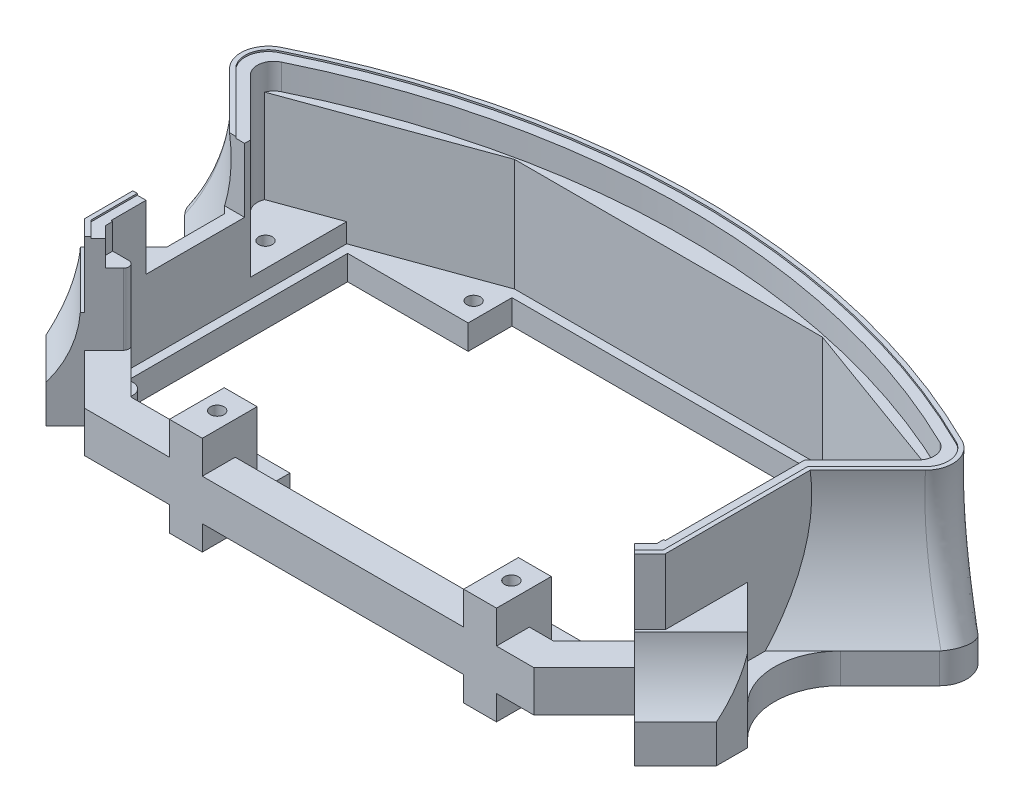
SolidWorks part; units mm, degrees
material "ABS"
ref_plane "Front Plane" through (0, 0, 0) normal (0, 0, 1) x (1, 0, 0)
ref_plane "Top Plane" through (0, 0, 0) normal (0, 1, 0) x (1, 0, 0)
ref_plane "Right Plane" through (0, 0, 0) normal (1, 0, 0) x (0, 0, -1)
sketch "Sketch1" plane through (0, 0, 0) normal (0, 1, 0) x (1, 0, 0)
  line L0 (53, 80) -> (53, 129.1478)
  line L1 (-53, 129.1478) -> (-53, 80)
  line L2 (-41, 68) -> (41, 68)
  line L3 (-53, 80) -> (-41, 68)
  line L4 (41, 68) -> (53, 80)
  circle A0 centre (0, 0) radius 140 construction
  arc A1 (53, 129.1478) -> (-53, 129.1478) centre (0, 0) ccw
  dimension "D1" = 280
  dimension "D3" = 139.6
  dimension "D2" = 106
  dimension "D4" = 68
  dimension "D5" = 80
  dimension "D6" = 135
  dimension "D7" = 135
extrude "Boss-Extrude1" add sketch "Sketch1" along normal blind 30
sketch "Sketch2" plane through (0, 30, 0) normal (0, 1, 0) x (1, 0, 0)
  line L0 (-49, 84) -> (49, 84)
  line L1 (49, 84) -> (49, 124)
  line L2 (49, 124) -> (27, 124)
  line L3 (27, 124) -> (27, 132)
  line L4 (27, 132) -> (-27, 132)
  line L5 (-27, 132) -> (-27, 124)
  line L6 (-27, 124) -> (-49, 124)
  line L7 (-49, 124) -> (-49, 84)
  line L12 (-53, 129.1478) -> (-53, 80) construction
  dimension "D1" = 48
  dimension "D2" = 98
  dimension "D3" = 8
  dimension "D4" = 84
  dimension "D5" = 22
  dimension "D6" = 4
extrude "Cut-Extrude1" cut sketch "Sketch2" against normal up to next
sketch "Sketch3" plane through (0, 30, 0) normal (0, 1, 0) x (1, 0, 0)
  line L0 (-50, 83) -> (50, 83) construction
  line L1 (50, 83) -> (50, 125) construction
  line L2 (50, 125) -> (28, 133) construction
  line L3 (28, 133) -> (-28, 133) construction
  line L4 (-28, 133) -> (-50, 125) construction
  line L5 (-50, 125) -> (-50, 83) construction
  line L7 (-49, 84) -> (-49, 124) construction
  line L8 (-50.6, 125.4203) -> (-50.6, 82.4)
  line L9 (-50.6, 82.4) -> (50.6, 82.4)
  line L10 (50.6, 82.4) -> (50.6, 125.4203)
  line L11 (50.6, 125.4203) -> (28.1057, 133.6)
  line L12 (28.1057, 133.6) -> (-28.1057, 133.6)
  line L13 (-28.1057, 133.6) -> (-50.6, 125.4203)
  line L16 (-49, 84) -> (49, 84) construction
  dimension "D1" = 50
  dimension "D2" = 22
  dimension "D3" = 8
  dimension "D4" = 1
  dimension "D5" = 1
  dimension "D6" = 100
  dimension "D7" = 0.6
extrude "Cut-Extrude2" cut sketch "Sketch3" against normal offset from surface (25.5 mm away) 4.5 up to face at (0, 0, -116)
sketch "Sketch5" plane through (0, 30, 0) normal (0, 1, 0) x (1, 0, 0)
  line L1 (-37.48, 68.91) -> (43.8, 68.91) construction
  line L2 (-37.48, 68.91) -> (-37.48, 122.25) construction
  line L3 (-37.48, 122.25) -> (43.8, 122.25) construction
  line L4 (43.8, 68.91) -> (43.8, 122.25) construction
  line L6 (-37.88, 68.51) -> (-37.88, 122.65)
  line L7 (-37.88, 122.65) -> (44.2, 122.65)
  line L8 (44.2, 68.51) -> (44.2, 122.65)
  line L9 (-37.88, 68.51) -> (44.2, 68.51)
  dimension "D1" = 68.91
  dimension "D2" = 43.8
  dimension "D3" = 81.28
  dimension "D4" = 53.34
  dimension "D5" = 0.4
extrude "Cut-Extrude4" cut sketch "Sketch5" against normal offset from surface (12 mm away) 18 up to face at (0, 0, -116)
sketch "Sketch4" plane through (0, 18, 0) normal (0, 1, 0) x (1, 0, 0)
  circle A0 centre (31.18, 73.72) radius 1.25
  circle A1 centre (-22.53, 73.72) radius 1.25
  dimension "D2" = 2.5
  dimension "D1" = 22.53
  dimension "D3" = 6.28
  dimension "D4" = 53.71
extrude "Cut-Extrude3" cut sketch "Sketch4" against normal up to next
sketch "Sketch6" plane through (0, 30, 0) normal (0, 1, 0) x (1, 0, 0)
  line L5 (53, 80) -> (53, 129.1478) construction
  line L6 (-53, 129.1478) -> (-53, 80) construction
  line L7 (-41, 68) -> (41, 68) construction
  line L8 (-53, 80) -> (-41, 68) construction
  line L9 (44.2, 71.2) -> (53, 80) construction
  line L25 (50.3, 81.1184) -> (50.3, 127.3245)
  line L26 (39.8816, 70.7) -> (50.3, 81.1184)
  line L27 (-39.8816, 70.7) -> (39.8816, 70.7)
  line L28 (-50.3, 81.1184) -> (-39.8816, 70.7)
  line L29 (-50.3, 127.3245) -> (-50.3, 81.1184)
  arc A1 (53, 129.1478) -> (-53, 129.1478) centre (0, 0) ccw construction
  arc A8 (50.3, 127.3245) -> (-50.3, 127.3245) centre (0, 0) ccw
  dimension "D3" = 2.7
  dimension "D1" = 2.7
  dimension "D2" = 2.7
  dimension "D4" = 2.7
  dimension "D5" = 2.7
  dimension "D6" = 2.7
extrude "Cut-Extrude5" cut sketch "Sketch6" against normal blind 5
sketch "Sketch7" plane through (0, 0, 0) normal (0, -1, 0) x (1, 0, 0)
  line L0 (73.4563, -118.7111) -> (53, -98.2548)
  line L1 (53, -80) -> (53, -129.1478) construction
  line L2 (53, -98.2548) -> (53, -129.1478)
  line L3 (0, 0) -> (103.3995, -103.3995) construction
  arc A0 (53, -129.1478) -> (73.4563, -118.7111) centre (0, 0) ccw
  arc A1 (-53, -129.1478) -> (53, -129.1478) centre (0, 0) ccw construction
  dimension "D1" = 45
  dimension "D2" = 32
extrude "Boss-Extrude2" add sketch "Sketch7" against normal up to surface (30 mm away) up to face at (0.5945, 30, -93.6394)
ref_plane "Plane1" through (96.0837, 0, -96.0837) normal (-0.7071, 0, 0.7071) x (0, -1, 0)
sketch "Sketch8" plane through (96.0837, 0, -96.0837) normal (-0.7071, 0, 0.7071) x (0, -1, 0)
  line L0 (-30, -32) -> (0, -32) construction
  circle A0 centre (-26, 0) radius 38
  dimension "D3" = 76
  dimension "D1" = 32
  dimension "D2" = 26
extrude "Cut-Extrude6" cut sketch "Sketch8" along normal up to surface (98.9296 mm away) up to face at (53, 18.75, -84.5637)
mirror "Mirror1" about plane through (0, 0, 0) normal (1, 0, 0) of "Boss-Extrude2"
ref_plane "Plane2" through (-96.0837, 0, -96.0837) normal (0.7071, 0, 0.7071) x (0, -1, 0)
sketch "Sketch9" plane through (-96.0837, 0, -96.0837) normal (0.7071, 0, 0.7071) x (0, -1, 0)
  line L0 (-30, 32) -> (0, 32) construction
  circle A0 centre (-26, 0) radius 38
  dimension "D1" = 76
  dimension "D2" = 32
  dimension "D3" = 26
extrude "Cut-Extrude7" cut sketch "Sketch9" along normal up to surface (22.9296 mm away) up to face at (-53, 18.75, -93.6911)
fillet "Fillet2" radius 5 4 edges at (69.0949, 16.9868, -121.3015) (73.4563, 2.753, -118.7111) (-73.4563, 2.753, -118.7111) (-68.9598, 17.6248, -121.3784)
sketch "Sketch11" plane through (0, 4.5, 0) normal (0, 1, 0) x (1, 0, 0)
  line L0 (-49, 124) -> (-27, 124) construction
  circle A0 centre (-30, 128) radius 1.25
  circle A1 centre (30, 128) radius 1.25
  dimension "D2" = 2.5
  dimension "D1" = 4
  dimension "D3" = 60
  dimension "D4" = 30
extrude "Cut-Extrude9" cut sketch "Sketch11" against normal up to next
sketch "Sketch12" plane through (0, 30, 0) normal (0, 1, 0) x (1, 0, 0)
  line L0 (-60.9187, 118.1786) -> (-50.3, 107.5599)
  line L2 (-50.3, 107.5599) -> (-50.3, 127.3245)
  line L3 (-63.5251, 116.9667) -> (-53, 106.4416) construction
  arc A0 (-50.3, 127.3245) -> (-60.1147, 122.9952) centre (0, 0) ccw
  arc A1 (-60.1147, 122.9952) -> (-60.9187, 118.1786) centre (-58.7974, 120.3) ccw
  arc A3 (62.1871, 124.9837) -> (-62.1871, 124.9837) centre (0, 0) ccw construction
  dimension "D1" = 2.7
  dimension "D2" = 3
extrude "Cut-Extrude10" cut sketch "Sketch12" against normal offset from surface (22 mm away) 8 up to face at (30, 0, -126.75)
sketch "Sketch14" plane through (0, 8, 0) normal (0, 1, 0) x (1, 0, 0)
  line L0 (-50.3, 127.3245) -> (-61.577, 123.2238)
  line L1 (-61.577, 123.2238) -> (-61.577, 121.4286)
  line L2 (-61.577, 121.4286) -> (-50.3, 125.5293)
  line L3 (-50.3, 125.5293) -> (-50.3, 127.3245)
  line L4 (-50.6, 125.4203) -> (-28.1057, 133.6) construction
  arc A0 (-60.1147, 122.9952) -> (-60.9187, 118.1786) centre (-58.7974, 120.3) ccw construction
extrude "Boss-Extrude3" add sketch "Sketch14" along normal up to surface (17 mm away) up to face at (0, 25, -130.4139)
mirror "Mirror2" about plane through (0, 0, 0) normal (1, 0, 0) of "Boss-Extrude3", "Cut-Extrude10"
sketch "Sketch15" plane through (0, 30, 0) normal (0, 1, 0) x (1, 0, 0)
  line L0 (-50.1716, 77.1716) -> (-43.3431, 84)
  line L1 (-53, 80) -> (-41, 68) construction
  line L2 (49, 84) -> (-49, 84) construction
  line L3 (-43.3431, 84) -> (43.3431, 84)
  line L4 (43.3431, 84) -> (50.1716, 77.1716)
  line L5 (41, 68) -> (41.51, 68.51) construction
  line L6 (50.1716, 77.1716) -> (41, 68)
  line L7 (41, 68) -> (-41, 68)
  line L8 (-41, 68) -> (-50.1716, 77.1716)
  dimension "D1" = 4
  dimension "D2" = 4
extrude "Cut-Extrude12" cut sketch "Sketch15" against normal up to surface (12 mm away) up to face at (-22.53, 18, -72.47)
sketch "Sketch16" plane through (0, 18, 0) normal (0, 1, 0) x (1, 0, 0)
  line L0 (-50.1716, 77.1716) -> (-44.9431, 82.4)
  line L1 (-44.9431, 82.4) -> (-25.53, 82.4)
  line L2 (50.6, 82.4) -> (-50.6, 82.4) construction
  line L3 (-25.53, 82.4) -> (-25.53, 68)
  line L4 (41, 68) -> (-41, 68) construction
  line L5 (-25.53, 68) -> (-41, 68)
  line L6 (-41, 68) -> (-50.1716, 77.1716) construction
  line L7 (-41, 68) -> (-50.1716, 77.1716)
  line L8 (44.9431, 82.4) -> (-44.9431, 82.4) construction
  line L9 (-19.53, 68) -> (28.18, 68)
  line L10 (-19.53, 68) -> (-19.53, 82.4)
  line L11 (-19.53, 82.4) -> (28.18, 82.4)
  line L12 (28.18, 68) -> (28.18, 82.4)
  line L13 (34.18, 82.4) -> (34.18, 68)
  line L14 (34.18, 68) -> (41, 68)
  line L15 (41, 68) -> (50.1716, 77.1716)
  line L16 (50.1716, 77.1716) -> (44.9431, 82.4)
  line L17 (44.9431, 82.4) -> (34.18, 82.4)
  circle A0 centre (31.18, 73.72) radius 1.25 construction
  circle A3 centre (-22.53, 73.72) radius 1.25 construction
  dimension "D1" = 3
  dimension "D2" = 3
  dimension "D3" = 3
  dimension "D4" = 3
extrude "Cut-Extrude13" cut sketch "Sketch16" against normal blind 6
sketch "Sketch20" plane through (0, 0, 0) normal (0, -1, 0) x (1, 0, 0)
  line L0 (-50.1716, -77.1716) -> (-41, -68)
  line L1 (-41, -68) -> (-25.53, -68)
  line L2 (-25.53, -68) -> (-25.53, -84)
  line L3 (-25.53, -84) -> (-43.3431, -84)
  line L4 (-43.3431, -84) -> (-50.1716, -77.1716)
  line L5 (-19.53, -84) -> (28.18, -84)
  line L6 (-19.53, -84) -> (-19.53, -68)
  line L7 (-19.53, -68) -> (28.18, -68)
  line L8 (28.18, -84) -> (28.18, -68)
  line L9 (34.18, -68) -> (34.18, -84)
  line L10 (34.18, -84) -> (43.3431, -84)
  line L11 (43.3431, -84) -> (50.1716, -77.1716)
  line L12 (50.1716, -77.1716) -> (41, -68)
  line L13 (41, -68) -> (34.18, -68)
  line L14 (-41, -68) -> (41, -68) construction
  line L15 (41, -68) -> (53, -80) construction
  line L16 (49, -84) -> (-49, -84) construction
  line L17 (-53, -80) -> (-41, -68) construction
extrude "Cut-Extrude17" cut sketch "Sketch20" against normal up to surface (4.5 mm away) up to face at (30, 4.5, -126.75)
fillet "Fillet4" radius 2 2 edges at (43.3431, 2.25, -84) (-43.3431, 2.25, -84)
sketch "Sketch17" plane through (0, 0, 0) normal (0, -1, 0) x (1, 0, 0)
  circle A0 centre (-55, -115) radius 1.25
  circle A1 centre (55, -115) radius 1.25
  dimension "D1" = 2.5
  dimension "D2" = 115
  dimension "D3" = 55
  dimension "D4" = 55
extrude "Cut-Extrude14" cut sketch "Sketch17" against normal blind 12
fillet "Fillet3" radius 1 2 edges at (44.9431, 18.5, -82.4) (-44.9431, 18.5, -82.4)
sketch "Sketch18" plane through (0, 18, 0) normal (0, 1, 0) x (1, 0, 0)
  line L0 (34.18, 82.4) -> (34.18, 68) construction
  line L1 (-25.53, 82.4) -> (34.18, 82.4)
  line L2 (-25.53, 82.4) -> (-25.53, 78)
  line L3 (-25.53, 78) -> (34.18, 78)
  line L4 (34.18, 82.4) -> (34.18, 78)
  line L5 (-19.53, 68) -> (-25.53, 68) construction
  dimension "D1" = 10
extrude "Cut-Extrude15" cut sketch "Sketch18" against normal up to surface (6 mm away) up to face at (-39.2781, 12, -76.4835)
sketch "Sketch19" plane through (0, 30, 0) normal (0, 1, 0) x (1, 0, 0)
  line L1 (-58, 106.7916) -> (-49, 106.7916)
  line L2 (-58, 106.7916) -> (-58, 88.7916)
  line L3 (-58, 88.7916) -> (-49, 88.7916)
  line L4 (-49, 106.7916) -> (-49, 88.7916)
  line L5 (-53, 106.4416) -> (-53, 80) construction
  line L6 (-49, 84) -> (-49, 124) construction
  circle A0 centre (-22.53, 73.72) radius 1.25 construction
  dimension "D1" = 15.0716
  dimension "D2" = 18
  dimension "D3" = 5
extrude "Cut-Extrude16" cut sketch "Sketch19" against normal up to surface (12 mm away) up to face at (-22.53, 18, -73)
sketch "Sketch21" plane through (0, 30, 0) normal (0, 1, 0) x (1, 0, 0)
  line L10 (-53, 105.5357) -> (-53, 88.7916) construction
  line L13 (52.2, 80) -> (52.2, 106.7729)
  line L14 (52.2, 106.7729) -> (62.9594, 117.5324)
  line L15 (-62.9594, 117.5324) -> (-52.7843, 107.3573)
  line L16 (52.2, 80.3314) -> (52.2, 106.7729)
  line L17 (52.2, 106.7729) -> (62.9594, 117.5324)
  line L18 (-62.9594, 117.5324) -> (-52.2, 106.7729)
  line L19 (-52.2, 106.7729) -> (-52.2, 80.3314)
  line L20 (-52.2, 80.3314) -> (-49.6059, 77.7373)
  line L21 (-46.6503, 80.6929) -> (-50.1716, 77.1716) construction
  line L22 (-49.6059, 77.7373) -> (49.6059, 77.7373)
  line L27 (50.1716, 77.1716) -> (46.6503, 80.6929) construction
  line L31 (49.6059, 77.7373) -> (52.2, 80.3314)
  line L33 (50.1716, 77.1716) -> (48.2624, 79.0808) construction
  line L34 (50.1716, 77.1716) -> (53, 80) construction
  line L35 (-53, 80) -> (-50.1716, 77.1716) construction
  arc A6 (61.8307, 124.2675) -> (-61.8307, 124.2675) centre (0, 0) ccw
  arc A7 (61.8307, 124.2675) -> (-61.8307, 124.2675) centre (0, 0) ccw
  spline S11 degree 3 poles (-2791.6803, -793.6282) (-151.1922, 208.4655) (47.8929, 98.3145) (63.3918, 118.0343) (63.4863, 118.1707) (63.7432, 118.5921) (63.884, 118.9004) (64.0846, 119.5295) (64.1477, 119.857) (64.1947, 120.5225) (64.1784, 120.8524) (64.0962, 121.3423) (64.0584, 121.5068) (63.9649, 121.8259) (63.9091, 121.9814) (63.7145, 122.4378) (63.5472, 122.7299) (63.1503, 123.2644) (62.9241, 123.5045) (41.0501, 141.8435) (-151.6347, -61.6595) (1792.5456, -2310.831) knots -9.381466 -9.381466 -9.381466 -9.381466 0.0625 0.0625 0.125 0.125 0.25 0.25 0.375 0.375 0.5 0.5 0.5625 0.5625 0.625 0.625 0.75 0.75 0.875 0.875 11.418904 11.418904 11.418904 11.418904 only from (62.9594, 117.5324) to (61.8307, 124.2675)
  spline S12 degree 3 poles (2933.466, 32.8068) (113.3304, -31.1396) (-41.1568, 137.8252) (-62.4023, 123.9288) (-62.5359, 123.8296) (-62.9156, 123.5123) (-63.1493, 123.2653) (-63.5445, 122.7339) (-63.711, 122.4452) (-63.974, 121.8299) (-64.0669, 121.5128) (-64.15, 121.0237) (-64.1683, 120.8561) (-64.1847, 120.5237) (-64.1829, 120.3586) (-64.16, 120.0292) (-64.1388, 119.8649) (-64.0769, 119.5398) (-64.0357, 119.3767) (-63.8846, 118.9013) (-63.7481, 118.6013) (-63.4897, 118.1756) (-63.394, 118.0374) (-47.2585, 97.4867) (150.4821, 235.4732) (2678.3171, -1087.2581) knots -9.468277 -9.468277 -9.468277 -9.468277 0.0625 0.0625 0.125 0.125 0.25 0.25 0.375 0.375 0.5 0.5 0.5625 0.5625 0.625 0.625 0.6875 0.6875 0.75 0.75 0.875 0.875 0.9375 0.9375 10.676928 10.676928 10.676928 10.676928 only from (-61.8307, 124.2675) to (-62.9594, 117.5324)
  spline S13 degree 3 poles (62.9594, 117.5324) (63.0781, 117.651) (63.188, 117.775) (63.3918, 118.0343) (63.4863, 118.1707) (63.7432, 118.5921) (63.884, 118.9004) (64.0846, 119.5295) (64.1477, 119.857) (64.1947, 120.5225) (64.1784, 120.8524) (64.0962, 121.3423) (64.0584, 121.5068) (63.9649, 121.8259) (63.9091, 121.9814) (63.7145, 122.4378) (63.5472, 122.7299) (63.1503, 123.2644) (62.9241, 123.5045) (62.4115, 123.9342) (62.1312, 124.118) (61.8307, 124.2675) knots 0 0 0 0 0.0625 0.0625 0.125 0.125 0.25 0.25 0.375 0.375 0.5 0.5 0.5625 0.5625 0.625 0.625 0.75 0.75 0.875 0.875 1 1 1 1
  spline S14 degree 3 poles (-61.8307, 124.2675) (-61.9813, 124.1925) (-62.1254, 124.1099) (-62.4023, 123.9288) (-62.5359, 123.8296) (-62.9156, 123.5123) (-63.1493, 123.2653) (-63.5445, 122.7339) (-63.711, 122.4452) (-63.974, 121.8299) (-64.0669, 121.5128) (-64.15, 121.0237) (-64.1683, 120.8561) (-64.1847, 120.5237) (-64.1829, 120.3586) (-64.16, 120.0292) (-64.1388, 119.8649) (-64.0769, 119.5398) (-64.0357, 119.3767) (-63.8846, 118.9013) (-63.7481, 118.6013) (-63.4897, 118.1756) (-63.394, 118.0374) (-63.1882, 117.7753) (-63.0779, 117.6508) (-62.9594, 117.5324) knots 0 0 0 0 0.0625 0.0625 0.125 0.125 0.25 0.25 0.375 0.375 0.5 0.5 0.5625 0.5625 0.625 0.625 0.6875 0.6875 0.75 0.75 0.875 0.875 0.9375 0.9375 1 1 1 1
  dimension "D2" = 0.8
  dimension "D3" = 0.8
  dimension "D1" = 0.8
extrude "Cut-Extrude18" cut sketch "Sketch21" against normal blind 0.3
sketch "Sketch22" plane through (0, 12, 0) normal (0, 1, 0) x (1, 0, 0)
  line L0 (-46.9147, 82.4) -> (-38.5147, 74)
  line L1 (47.3574, 82.4) -> (-47.3574, 82.4) construction
  line L2 (-38.5147, 74) -> (-25.53, 74)
  line L3 (-25.53, 68) -> (-25.53, 78) construction
  line L4 (-25.53, 74) -> (-25.53, 78)
  line L5 (-25.53, 78) -> (-19.53, 78)
  line L6 (-19.53, 78) -> (-19.53, 74)
  line L7 (-19.53, 78) -> (-19.53, 68) construction
  line L8 (-19.53, 74) -> (28.18, 74)
  line L9 (28.18, 68) -> (28.18, 78) construction
  line L10 (28.18, 74) -> (28.18, 78)
  line L11 (28.18, 78) -> (34.18, 78)
  line L12 (34.18, 78) -> (34.18, 74)
  line L13 (34.18, 78) -> (34.18, 68) construction
  line L14 (34.18, 74) -> (38.5147, 74)
  line L15 (38.5147, 74) -> (46.9147, 82.4)
  line L16 (46.9147, 82.4) -> (-46.9147, 82.4)
  line L17 (-41, 68) -> (-25.53, 68) construction
  line L19 (-50.1716, 77.1716) -> (-41, 68) construction
  line L20 (41, 68) -> (50.1716, 77.1716) construction
  dimension "D1" = 6
  dimension "D2" = 6
  dimension "D3" = 6
extrude "Cut-Extrude19" cut sketch "Sketch22" against normal up to surface (7.5 mm away) up to face at (-22.53, 4.5, -83.2)
sketch "Sketch23" plane through (0, 0, 0) normal (0, -1, 0) x (1, 0, 0)
  line L0 (50.1716, -77.1716) -> (53.7071, -73.636)
  line L1 (53.7071, -73.636) -> (64.0355, -83.9645)
  line L2 (64.0355, -83.9645) -> (53, -95)
  line L3 (53, -80) -> (53, -98.2548) construction
  line L4 (53, -95) -> (53, -80)
  line L5 (53, -80) -> (50.1716, -77.1716)
  line L6 (46.7574, -80.5858) -> (50.1716, -77.1716) construction
  dimension "D1" = 5
  dimension "D2" = 15
extrude "Boss-Extrude4" add sketch "Sketch23" against normal blind 18
sketch "Sketch24" plane through (74, 0, -74) normal (0.7071, 0, -0.7071) x (-0.7071, 0, -0.7071)
  circle A0 centre (0, 19) radius 18.55
  dimension "D1" = 37.1
  dimension "D2" = 19
extrude "Cut-Extrude20" cut sketch "Sketch24" against normal up to next
sketch "Sketch25" plane through (0, 0, 0) normal (0, 0, 1) x (1, 0, 0)
  line L1 (61.2, 0) -> (64.0355, 0)
  line L2 (61.2, 0) -> (61.2, 18)
  line L3 (61.2, 18) -> (64.0355, 18)
  line L4 (64.0355, 0) -> (64.0355, 18)
  line L5 (46.7574, 0) -> (53.7071, 0) construction
  line L7 (64.0355, 6.9368) -> (64.0355, 0) construction
  line L8 (68.8826, 0) -> (53, 0) construction
  line L9 (50.5738, 18) -> (60.9022, 18) construction
  line L10 (53, 30) -> (53, 18) construction
  dimension "D1" = 8.2
extrude "Cut-Extrude21" cut sketch "Sketch25" against normal up to next
mirror "Mirror3" about plane through (0, 0, 0) normal (1, 0, 0) of "Cut-Extrude20", "Cut-Extrude21", "Boss-Extrude4"
sketch "Sketch26" plane through (0, 0, 0) normal (0, -1, 0) x (1, 0, 0)
  line L0 (53, -95) -> (61.2, -86.8) construction
  line L1 (68.8826, -114.1374) -> (53, -98.2548) construction
  line L2 (59.8579, -88.1421) -> (53, -95)
  line L3 (53, -95) -> (53, -98.2548)
  line L4 (53, -98.2548) -> (59.8579, -105.1127)
  line L5 (-53, -95) -> (-61.2, -86.8) construction
  line L6 (-68.8826, -114.1374) -> (-53, -98.2548) construction
  line L7 (-59.8579, -88.1421) -> (-53, -95)
  line L8 (-53, -95) -> (-53, -98.2548)
  line L9 (-53, -98.2548) -> (-59.8579, -105.1127)
  arc A0 (59.8579, -88.1421) -> (59.8579, -105.1127) centre (68.3431, -96.6274) ccw
  arc A1 (-59.8579, -88.1421) -> (-59.8579, -105.1127) centre (-68.3431, -96.6274) cw
  dimension "D1" = 12
extrude "Boss-Extrude5" add sketch "Sketch26" against normal up to vertex (5.5061 mm away) up to point (53, 5.5061, -98.2548)
ref_plane "Plane3" through (0, 0, -139.6) normal (0, 0, -1) x (-1, 0, 0)
sketch "Sketch28" plane through (0, 0, -139.6) normal (0, 0, 1) x (1, 0, 0)
  line L0 (113.7971, -275.5265) -> (780.4638, -275.5265) construction
  line L1 (3.8, 40) -> (-6.948, 40) construction
  line L2 (-67.7745, 0) -> (67.7745, 0) construction
  line L3 (19, 24.8) -> (13.8, 30)
  line L4 (62.1871, 30) -> (-62.1871, 30) construction
  line L5 (13.8, 30) -> (3.052, 30)
  line L6 (-6.948, 40) -> (8.252, 24.8) construction
  line L7 (8.252, 24.8) -> (-19, 24.8)
  line L8 (-19, 24.8) -> (-19, 17.2)
  line L9 (-19, 17.2) -> (-3.8, 2)
  line L10 (-3.8, 2) -> (20, 2)
  line L11 (20, 2) -> (12.4, 9.6)
  line L12 (12.4, 9.6) -> (-0.652, 9.6)
  line L13 (-0.652, 9.6) -> (-8.252, 17.2)
  line L14 (-8.252, 17.2) -> (19, 17.2)
  line L15 (19, 17.2) -> (19, 24.8)
  line L16 (19, 24.8) -> (3.8, 40) construction
  line L17 (-5.348, 32.4) -> (-12.948, 40) construction
  line L18 (-12.948, 40) -> (-23.696, 40) construction
  line L19 (-23.696, 40) -> (-16.096, 32.4) construction
  line L20 (-16.096, 32.4) -> (-5.348, 32.4) construction
  line L21 (3.052, 30) -> (8.252, 24.8)
  dimension "D2" = 45
  dimension "D3" = 7.6
  dimension "D4" = 7.6
  dimension "D5" = 7.6
  dimension "D6" = 7.6
  dimension "D7" = 38
  dimension "D8" = 7.6
  dimension "D9" = 7.6
  dimension "D10" = 38
  dimension "D11" = 6
  dimension "D12" = 7.6
  dimension "D13" = 2
  dimension "D14" = 19
  dimension "D15" = 1
wrap "Wrap11" [suppressed] sketch "Sketch28" source sketch "Sketch28" thickness 0.4 parameters "D1"=0.4
